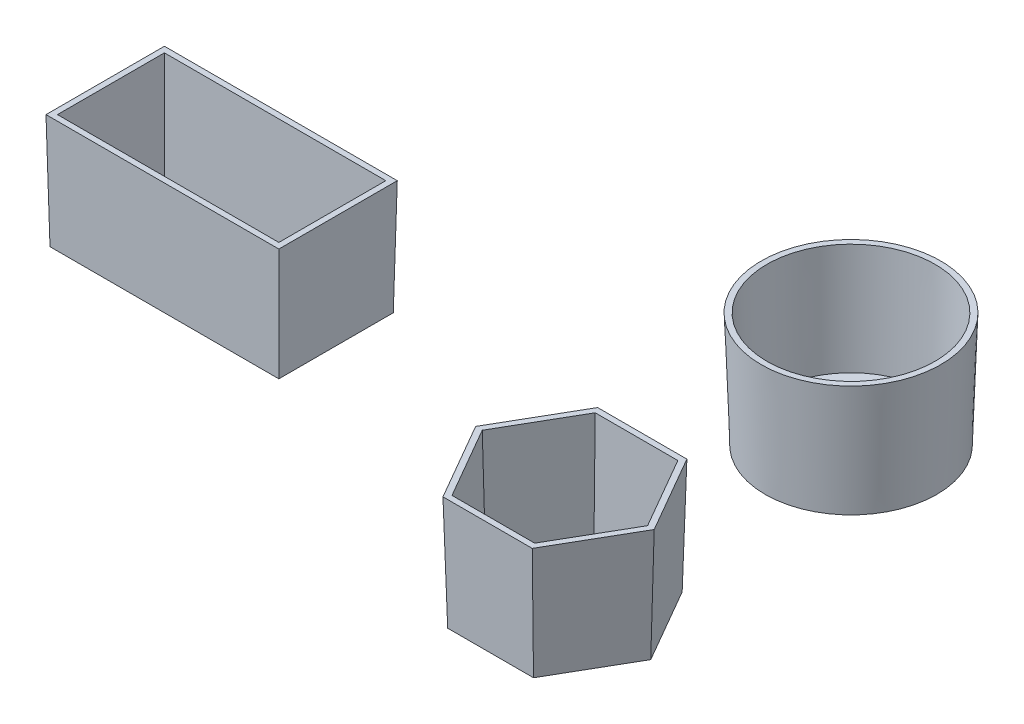
SolidWorks part; units mm, degrees
ref_plane "Alzado" through (0, 0, 0) normal (0, 0, 1) x (1, 0, 0)
ref_plane "Planta" through (0, 0, 0) normal (0, 1, 0) x (1, 0, 0)
ref_plane "Vista lateral" through (0, 0, 0) normal (1, 0, 0) x (0, 0, -1)
sketch "Croquis1" plane through (0, 0, 0) normal (0, 1, 0) x (1, 0, 0)
  line L1 (-65, -10) -> (-25, -10)
  line L2 (-65, -10) -> (-65, 10)
  line L3 (-65, 10) -> (-25, 10)
  line L4 (-25, -10) -> (-25, 10)
  line L5 (-65, -10) -> (-25, 10) construction
  line L6 (-65, 10) -> (-25, -10) construction
  line L13 (50, -20) -> (42.5, -7.0096)
  line L14 (42.5, -7.0096) -> (27.5, -7.0096)
  line L15 (27.5, -7.0096) -> (20, -20)
  line L16 (20, -20) -> (27.5, -32.9904)
  line L17 (27.5, -32.9904) -> (42.5, -32.9904)
  line L18 (42.5, -32.9904) -> (50, -20)
  circle A0 centre (35, 30) radius 15
  circle A1 centre (35, -20) radius 12.9904 construction
  point P2 (-45, 0)
  dimension "D8" = 30
  dimension "D1" = 40
  dimension "D2" = 20
  dimension "D3" = 25
  dimension "D4" = 10
  dimension "D5" = 15
  dimension "D6" = 20
  dimension "D7" = 35
  dimension "D9" = 35
  dimension "D10" = 30
extrude "Saliente-Extruir1" add sketch "Croquis1" along normal blind 20 draft 1 contours L1 L4 L3 L2 region at (-45, 0, 0) draft outward yes
extrude "Saliente-Extruir2" add sketch "Croquis1<3>" along normal blind 20 draft 2 separate body contours A0 region at (35, 0, -30) draft outward yes
sketch "Croquis1<3>" plane through (0, 0, 0) normal (0, 1, 0) x (1, 0, 0) same geometry as "Croquis1"
extrude "Saliente-Extruir3" add sketch "Croquis1<4>" along normal blind 20 draft 1.5 separate body contours L17 L18 L13 L14 L15 L16 region at (35, 0, 20) draft outward yes
sketch "Croquis1<4>" plane through (0, 0, 0) normal (0, 1, 0) x (1, 0, 0) same geometry as "Croquis1"
shell "Vaciado1" thickness 1 removed face at (-45, 20, 0)
shell "Vaciado2" thickness 1 removed face at (35, 20, 20)
shell "Vaciado3" thickness 1 removed face at (35, 20, -14.3016)
sketch "Croquis2" plane through (0, 0, 0) normal (0, 1, 0) x (1, 0, 0)
  line L3 (0, 0) -> (-25, 0)
  line L4 (-25, -10) -> (-25, 10) construction
  line L5 (0, 0) -> (23.75, -13.5048)
  line L6 (27.5, -7.0096) -> (20, -20) construction
  line L7 (0, 0) -> (23.6112, 20.2381)
  circle A0 centre (35, 30) radius 15 construction
